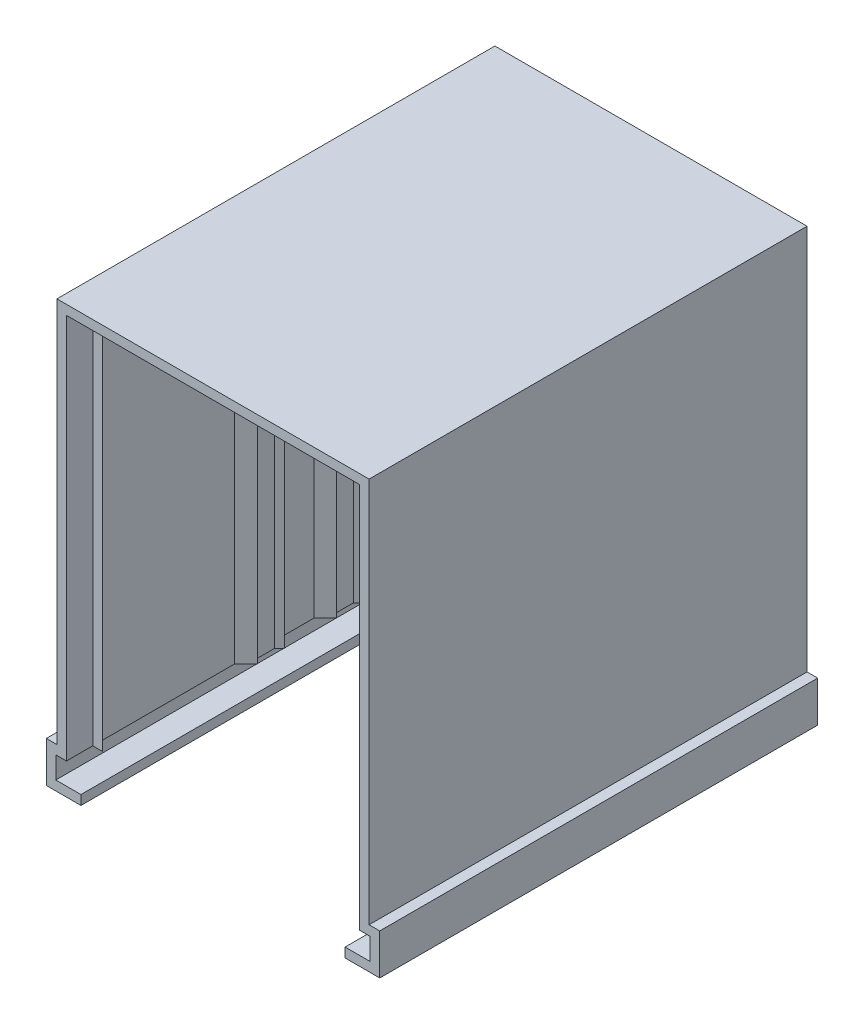
SolidWorks part; units mm, degrees
ref_plane "Front Plane" through (0, 0, 0) normal (0, 0, 1) x (1, 0, 0)
ref_plane "Top Plane" through (0, 0, 0) normal (0, 1, 0) x (1, 0, 0)
ref_plane "Right Plane" through (0, 0, 0) normal (1, 0, 0) x (0, 0, -1)
sketch "Sketch1" plane through (0, 0, 0) normal (0, 0, 1) x (1, 0, 0)
  line L0 (-14.81, 0.1) -> (-15.885, 0.1)
  line L1 (-15.885, 0.1) -> (-15.885, -2.1)
  line L7 (-14.81, 39.1) -> (-14.81, 0.1)
  line L8 (-14.71, 0) -> (-15.785, 0)
  line L9 (-15.785, 0) -> (-15.785, -2)
  line L10 (-15.785, -2) -> (15.785, -2)
  line L11 (15.785, -2) -> (15.785, 0)
  line L12 (15.785, 0) -> (14.71, 0)
  line L13 (14.71, 0) -> (14.71, 39)
  line L14 (14.71, 39) -> (-14.71, 39)
  line L15 (-14.71, 39) -> (-14.71, 0)
  line L16 (-14.71, 0) -> (-15.785, 0) construction
  line L17 (-15.785, 0) -> (-15.785, -2) construction
  line L18 (-15.785, -2) -> (15.785, -2) construction
  line L19 (15.785, -2) -> (15.785, 0) construction
  line L20 (15.785, 0) -> (14.71, 0) construction
  line L21 (14.71, 0) -> (14.71, 39) construction
  line L22 (14.71, 39) -> (-14.71, 39) construction
  line L23 (-14.71, 39) -> (-14.71, 0) construction
  line L24 (-15.885, -2.1) -> (15.885, -2.1) construction
  line L25 (-15.885, -2.1) -> (-13.345, -2.1)
  line L26 (-14.81, 39.1) -> (0, 39.1)
  line L27 (14.81, 0.1) -> (14.81, 39.1) construction
  line L28 (15.885, 0.1) -> (14.81, 0.1) construction
  line L29 (15.885, -2.1) -> (15.885, 0.1) construction
  line L30 (0, 43.8511) -> (0, -0.5601) construction
  line L31 (-15.77, 40.06) -> (0, 40.06)
  line L32 (14.81, 39.1) -> (-14.81, 39.1) construction
  line L33 (-15.77, 40.06) -> (-15.77, 1.06)
  line L34 (-15.77, 1.06) -> (-16.845, 1.06)
  line L35 (-16.845, 1.06) -> (-16.845, -3.06)
  line L36 (-16.845, -3.06) -> (-13.345, -3.06)
  line L37 (-13.345, -3.06) -> (-13.345, -2.1)
  line L38 (14.81, 39.1) -> (0, 39.1)
  line L39 (14.81, 39.1) -> (14.81, 0.1)
  line L40 (14.81, 0.1) -> (15.885, 0.1)
  line L41 (15.885, 0.1) -> (15.885, -2.1)
  line L42 (15.885, -2.1) -> (13.345, -2.1)
  line L43 (13.345, -3.06) -> (13.345, -2.1)
  line L44 (16.845, -3.06) -> (13.345, -3.06)
  line L45 (16.845, 1.06) -> (16.845, -3.06)
  line L46 (15.77, 1.06) -> (16.845, 1.06)
  line L47 (15.77, 40.06) -> (15.77, 1.06)
  line L48 (15.77, 40.06) -> (0, 40.06)
  dimension "D4" = 3.5
  dimension "D1" = 0
  dimension "D2" = 0.1
  dimension "D3" = 0.96
extrude "Boss-Extrude1" add sketch "Sketch1" against normal up to surface (44.25 mm away)
sketch "Sketch2" plane through (0, 39.1, 0) normal (0, -1, 0) x (1, 0, 0)
  line L0 (-14.81, -2.66) -> (-13.81, -2.66)
  line L1 (-14.81, -44.25) -> (-14.81, 0) construction
  line L2 (-13.81, -2.66) -> (-14.81, -3.66)
  line L3 (-14.81, -3.66) -> (-14.81, -2.66)
  line L4 (14.71, -2.56) -> (-14.71, -2.56) construction
  line L5 (0, 0) -> (0, -7.6274) construction
  line L6 (14.81, -3.66) -> (14.81, -2.66)
  line L7 (13.81, -2.66) -> (14.81, -3.66)
  line L8 (14.81, -2.66) -> (13.81, -2.66)
  dimension "D1" = 1
  dimension "D2" = 45
  dimension "D3" = 0.1
extrude "Boss-Extrude2" add sketch "Sketch2" along normal offset from surface (39 mm away) 0.1
sketch "Sketch3" plane through (0, 39.1, 0) normal (0, -1, 0) x (1, 0, 0)
  line L2 (-14.81, -44.25) -> (-14.81, -3.66) construction
  line L3 (-14.81, -32.99) -> (-14.81, -38.01)
  line L5 (-14.15, -36.35) -> (-14.15, -34.65)
  line L7 (-14.05, -34.75) -> (-14.05, -36.25) construction
  line L8 (-14.05, -34.75) -> (-14.05, -36.25) construction
  line L9 (-14.05, -35.5) -> (13.7849, -35.5) construction
  line L10 (0, 0) -> (0, -60.4865) construction
  line L11 (-14.15, -34.65) -> (-13.65, -34.15)
  line L12 (-13.65, -34.15) -> (-14.81, -32.99)
  line L13 (-13.65, -36.85) -> (-14.81, -38.01)
  line L14 (-14.15, -36.35) -> (-13.65, -36.85)
  line L15 (14.15, -36.35) -> (13.65, -36.85)
  line L16 (13.65, -36.85) -> (14.81, -38.01)
  line L17 (13.65, -34.15) -> (14.81, -32.99)
  line L18 (14.15, -34.65) -> (13.65, -34.15)
  line L19 (14.15, -36.35) -> (14.15, -34.65)
  line L20 (14.81, -32.99) -> (14.81, -38.01)
  point P0 (-14.15, -34.2409)
  point P6 (14.15, -35.5)
  point P7 (-14.81, -35.5)
  point P18 (-14.15, -35.5)
  point P19 (14.81, -35.5)
  dimension "D1" = 0.1
  dimension "D2" = 45
  dimension "D3" = 45
  dimension "D4" = 0.1
  dimension "D5" = 0.5
extrude "Boss-Extrude3" add sketch "Sketch3" along normal offset from surface (39 mm away) 0.1
pattern_linear "LPattern1" count 2 spacing 7 along (0, 0, -1) count 3 spacing 8 along (0, 0, 1) skipping (1, 1), (1, 2) of "Boss-Extrude3"
split "Split1" bodies to split 104 resulting bodies 105 106 107 split by face at (0, 10.0236, -44.25)
delete or keep bodies "Body-Delete/Keep 1" type delete bodies bodies 107 106
equation "\"offset\"=0.1"
equation "\"D1@Boss-Extrude2\"=\"offset\""
equation "\"D1@Sketch3\"=\"offset\""
equation "\"D4@Sketch3\"=\"offset\""
equation "\"D1@Boss-Extrude3\"=\"offset\""
